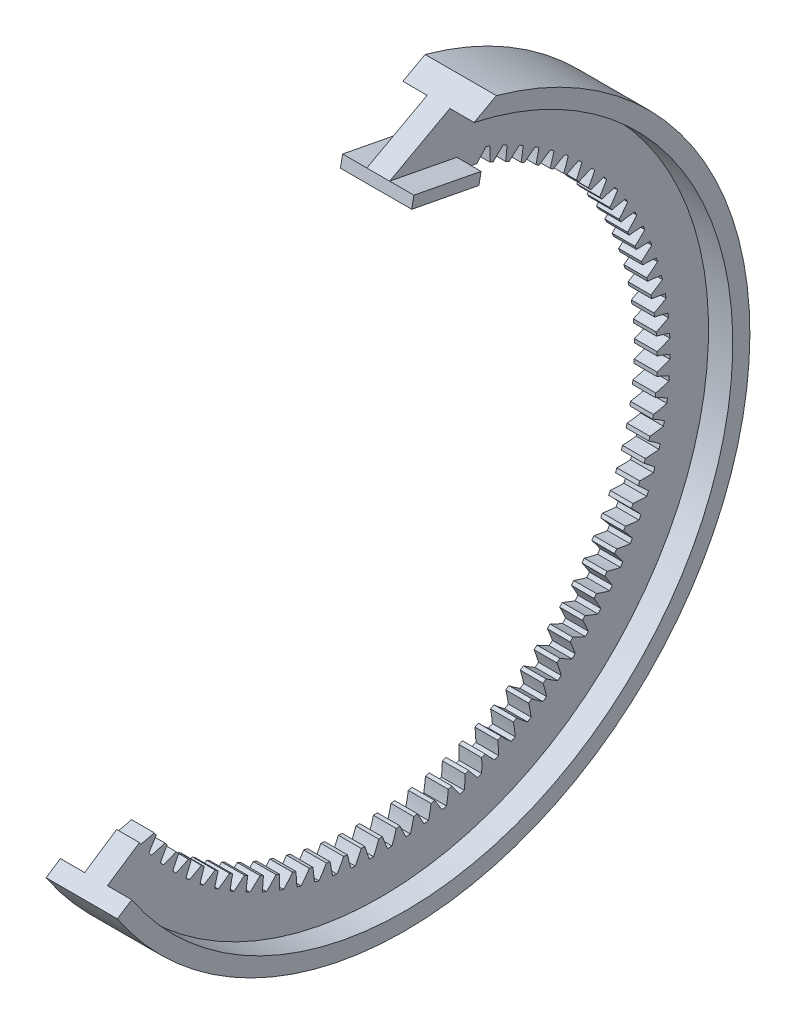
SolidWorks part; units mm, degrees
material "ABS"
ref_plane "Plane1" through (0, 0, 0) normal (0, 0, 1) x (1, 0, 0)
ref_plane "Plane2" through (0, 0, 0) normal (0, 1, 0) x (1, 0, 0)
ref_plane "Plane3" through (0, 0, 0) normal (1, 0, 0) x (0, 0, -1)
other "Configuration Table"
sketch "HoldingSke" plane through (0, 0, 0) normal (0, 1, 0) x (1, 0, 0)
  line L0 (0, 0) -> (-0.0262, -0.4993)
  line L1 (-15, 0) -> (100, 0) construction
  line L2 (0, 0) -> (-2.1039, 2.3779)
  line L3 (0, 0) -> (-11.863, 4.5341)
  line L4 (0, 0) -> (-1.351, 8.5297)
  line L5 (0, 0) -> (-23.7986, -8.8762)
  line L6 (0, 0) -> (-10.5278, -7.1032)
  line L7 (-2.1039, 2.3779) -> (3.3635, 27.1825)
  line L8 (-76.2, 4.3779) -> (-54.61, 4.3779)
  line L9 (-71.009, 38.7566) -> (-53.1078, 45.2721)
  line L10 (-76.2, 71.12) -> (104.1128, 71.12)
  line L11 (0, 0) -> (-8, 0)
  line L12 (-76.2, 101.6) -> (-76.133, 101.6)
  line L13 (24.9733, 27.94) -> (52.9518, 28.4284)
  line L14 (24.9733, 27.94) -> (24.9743, 27.94)
  line L15 (24.9733, 27.94) -> (100.4006, 29.5858)
  circle A0 centre (0, 0) radius 105
  circle A1 centre (0, 0) radius 12.7
  circle A2 centre (0, 0) radius 12.7
  dimension "MHD" = 25.4
  dimension "Hub_dia" = 25.4
  dimension "Diameter" = 210
  dimension "Num_teeth" = 99
  dimension "Pitch" = 0.5
  dimension "Overall_len" = 25.4
  dimension "Show_teeth" = 93
  dimension "Thickness" = 12.7
  dimension "OAL" = 25.4001
  dimension "T_dim" = 21.59
  dimension "Ap" = 20
  dimension "H" = 19.05
  dimension "Pitch_radius" = 180.3128
  dimension "Width" = 8
  dimension "Backlash" = 0.067
  dimension "Addendum_fac" = 1
  dimension "Dedendum_fac" = 1.25
  dimension "Clearance_fac" = 0.25
  dimension "Dedendum_add" = 0.001
  dimension "Module" = 2
ref_axis "Assi1" through (0, 0, 0) along (0, 1, 0)
sketch "BasProSke" plane through (0, 0, 0) normal (0, 1, 0) x (1, 0, 0)
  line L0 (-10, 0) -> (60, 0) construction
  line L1 (0, 97) -> (0, 105)
  line L2 (0, 97) -> (8, 97)
  line L3 (8, 97) -> (8, 105)
  line L4 (8, 105) -> (0, 105)
  dimension "Diameter" = 210
  dimension "Thickness" = 8
  dimension "Inside_diameter" = 194
revolve "Base-Revolve" add sketch "BasProSke" angle 360 about L0
sketch "TooCutSke" plane through (0, 0, 0) normal (1, 0, 0) x (0, 0, -1)
  line L3 (1.7382, 98.9847) -> (1.7382, 53.6633) construction
  line L4 (0, 0) -> (0, 59.563) construction
  line L5 (0, 0) -> (-2.1679, 68.2931) construction
  line L6 (-44.8809, 82.3441) -> (35.1673, 84.8851) construction
  circle A0 centre (0, 0) radius 99 construction
  circle A1 centre (0, 0) radius 101.501 construction
  circle A2 centre (0, 0) radius 83.7266 construction
  circle A3 centre (0, 0) radius 96.9746 construction
  arc A4 (2.4169, 96.9445) -> (0.7631, 101.4981) centre (-44.8809, 82.3441) ccw
  arc A5 (2.4169, 96.9445) -> (-2.4169, 96.9445) centre (0, 0) ccw
  arc A6 (0.7631, 101.4981) -> (-0.7631, 101.4981) centre (0, 0) ccw
  arc A7 (-0.7631, 101.4981) -> (-2.4169, 96.9445) centre (44.8809, 82.3441) ccw
  dimension "Pitch_dia" = 198
  dimension "Base_dia" = 167.4532
  dimension "Root_dia" = 203.002
  dimension "Overcut_dia" = 193.9492
  dimension "Flank_rad" = 49.5
  dimension "Half_ang" = 1.818
  dimension "Half_CT" = 1.7382
extrude "ToothCut" cut sketch "TooCutSke" along normal through all
fillet "Breaks" [suppressed] radius 0.2
fillet "RootFillets" [suppressed] radius 0.501
pattern_circular "TeethCuts" count 94 every 3.636 about axis through (-10, 0, 0) along (1, 0, 0) of "ToothCut"
sketch "Schizzo1" plane through (8, 0, 0) normal (1, 0, 0) x (0, 0, -1)
  line L0 (18.3574, 95.2471) -> (0, 0) construction
  line L1 (0, 0) -> (-87.4801, -58.0709)
  line L2 (18.3574, 95.2471) -> (19.8714, 103.1025) construction
  line L3 (0, 0) -> (2.409, 96.9701)
  line L4 (2.409, 96.9701) -> (2.6077, 104.9676)
  line L5 (0, 0) -> (76.0672, 72.3794) construction
  arc A0 (33.8037, 90.9193) -> (2.409, 96.9701) centre (0, 0) ccw construction
  circle A1 centre (0, 0) radius 105 construction
  arc A2 (2.6077, 104.9676) -> (-87.4801, -58.0709) centre (0, 0) ccw
  dimension "D1" = 125
  dimension "D2" = 45
extrude "Taglio-Estrusione1" cut sketch "Schizzo1" against normal blind 10
sketch "Schizzo2" plane through (8, 0, 0) normal (1, 0, 0) x (0, 0, -1)
  line L2 (2.409, 96.9701) -> (33.8037, 90.9193)
  arc A0 (33.8037, 90.9193) -> (2.409, 96.9701) centre (0, 0) ccw
extrude "Estrusione-Estrusione1" add sketch "Schizzo2" against normal blind 8
sketch "Schizzo3" plane through (0, 93.9447, -18.1064) normal (0, -0.9819, 0.1893) x (1, 0, 0)
  line L0 (0, 15.9862) -> (8, 15.9862) construction
  line L1 (-8.5, -8.0138) -> (16.5, -8.0138)
  line L2 (-8.5, -8.0138) -> (-8.5, 15.9862)
  line L3 (-8.5, 15.9862) -> (16.5, 15.9862)
  line L4 (16.5, -8.0138) -> (16.5, 15.9862)
  line L5 (0, 15.9862) -> (0, -8.0138)
  line L6 (0, 15.9862) -> (0, -15.9862) construction
  line L7 (8, 15.9862) -> (8, -8.0138)
  line L8 (8, 15.9862) -> (8, -15.9862) construction
  point P6 (4, 15.9862)
  point P7 (4, 15.9862)
  line M5 (8, -15.9862) -> (8, 15.9862)
  line M7 (0, 15.9862) -> (0, -15.9862)
  dimension "D1" = 25
  dimension "D2" = 24
extrude "Estrusione-Estrusione2" add sketch "Schizzo3" against normal blind 4 contours L3 L2 L1 M7 | L1 L4 L3 M5 region at (-4.25, 94.6991, -14.1921) region at (12.25, 94.6991, -14.1921)
sketch "Schizzo4" plane through (0, 0, 0) normal (0, 0.0248, 0.9997) x (1, 0, 0)
  line L0 (0, 105) -> (0, 115)
  line L1 (0, 115) -> (-8.5, 115)
  line L2 (-8.5, 115) -> (-8.5, 121)
  line L3 (-8.5, 121) -> (16.5, 121)
  line L4 (16.5, 121) -> (16.5, 115)
  line L5 (16.5, 115) -> (8, 115)
  line L6 (8, 115) -> (8, 105)
  line L9 (4, 121) -> (4, 105) construction
  line L10 (0, 105) -> (8, 105) construction
  line L11 (0, 105) -> (8, 105)
  line L12 (-101.9075, 0) -> (149.4298, 0) construction
  dimension "D1" = 10
  dimension "D2" = 6
  dimension "D3" = 25
revolve "Rivoluzione1" add sketch "Schizzo4" angle 235 about L12 reverse direction yes
sketch "Schizzo5" plane through (16.5, 0, 0) normal (1, 0, 0) x (0, 0, -1)
  line L0 (3.166, 100.8978) -> (32.1079, 116.6623)
  line L1 (3.166, 100.8978) -> (2.409, 96.9701)
  line L2 (2.409, 96.9701) -> (3.005, 120.9627)
  arc A1 (-100.8104, -66.9198) -> (3.005, 120.9627) centre (0, 0) ccw construction
  arc A2 (32.1079, 116.6623) -> (3.005, 120.9627) centre (0, 0) ccw
  dimension "D1" = 60
extrude "Taglio-Estrusione2" cut sketch "Schizzo5" against normal blind 25
equation "' \"Module@HoldingSke\" = 6.35"
equation "' \"Num_teeth@HoldingSke\" = 24"
equation "' \"Ap@HoldingSke\" =  14.5"
equation "' \"Ap@HoldingSke\" = 14.5"
equation "' \"Width@HoldingSke\" = 12"
equation "' \"Diameter@HoldingSke\" = 8 * 25.4"
equation "' \"Show_teeth@HoldingSke\" = 100"
equation "' \"Backlash@HoldingSke\" = 0.009 * 25.4"
equation "' \"Addendum_fac@HoldingSke\" = 1.0"
equation "' \"Dedendum_fac@HoldingSke\" = 1.25"
equation "' \"Dedendum_add@HoldingSke\" = 0.00005 * 25.4"
equation "' \"Clearance_fac@HoldingSke\" = 0.25"
equation "\"Pitch@HoldingSke\" = 1 / \"Module@HoldingSke\" "
equation "\"Overcut_dia@TooCutSke\" = (\"Num_teeth@HoldingSke\" - 2 * \"Addendum_fac@HoldingSke\") / \"Pitch@HoldingSke\" - 0.002 * 25.4"
equation "\"Pitch_dia@TooCutSke\" = \"Num_teeth@HoldingSke\" / \"Pitch@HoldingSke\""
equation "\"Base_dia@TooCutSke\" = \"Num_teeth@HoldingSke\" / \"Pitch@HoldingSke\" * cos((\"Ap@HoldingSke\"  * 3.14159265 / 180)) * 0.90"
equation "\"Root_dia@TooCutSke\" = \"Num_teeth@HoldingSke\"  / \"Pitch@HoldingSke\" + 2 *  \"Dedendum_fac@HoldingSke\"/ \"Pitch@HoldingSke\" + \"Dedendum_add@HoldingSke\" * 2"
equation "\"Half_ang@TooCutSke\" = 180 / \"Num_teeth@HoldingSke\""
equation "\"Half_CT@TooCutSke\" = \"Num_teeth@HoldingSke\" / \"Pitch@HoldingSke\" * sin((3.14159265 / 2 / \"Num_teeth@HoldingSke\")) / 2 + 10 * \"Backlash@HoldingSke\" / 4"
equation "\"Flank_rad@TooCutSke\" = \"Num_teeth@HoldingSke\" / \"Pitch@HoldingSke\" / 4"
equation "\"Radius@RootFillets\"= \"Clearance_fac@HoldingSke\" / \"Pitch@HoldingSke\" + \"Dedendum_add@HoldingSke\""
equation "\"Break_rad@Breaks\" = 0.02 / \"Pitch@HoldingSke\" * 5"
equation "\"Num_teeth@TeethCuts\" = int( \"Show_teeth@HoldingSke\" ) + 1"
equation "\"Num_teeth@TeethCuts\" = ((sgn( \"Num_teeth@TeethCuts\" - \"Num_teeth@HoldingSke\" )-1)*( \"Num_teeth@TeethCuts\" - \"Num_teeth@HoldingSke\" ))/-2+ \"Num_teeth@HoldingSke\""
equation "\"Num_teeth@TeethCuts\" = ((sgn( \"Num_teeth@TeethCuts\" - 2.0)+1)*( \"Num_teeth@TeethCuts\" - 2.0))/2 +2.0"
equation "\"Angle@TeethCuts\" = 360.0 / \"Num_teeth@HoldingSke\""
equation "\"Diameter@BasProSke\" = \"Num_teeth@HoldingSke\"  / \"Pitch@HoldingSke\" + 2 *  \"Dedendum_fac@HoldingSke\"/ \"Pitch@HoldingSke\" + \"Dedendum_add@HoldingSke\" * 2 + 0.002 * 25.4"
equation "\"Diameter@BasProSke\" = ((sgn( \"Diameter@BasProSke\"  - \"Diameter@HoldingSke\" )+1)*( \"Diameter@BasProSke\"  - \"Diameter@HoldingSke\" ))/2 + \"Diameter@HoldingSke\""
equation "\"Inside_diameter@BasProSke\" =  (\"Num_teeth@HoldingSke\" - 2 * \"Addendum_fac@HoldingSke\") / \"Pitch@HoldingSke\" "
equation "\"Thickness@BasProSke\"  = \"Width@HoldingSke\""
